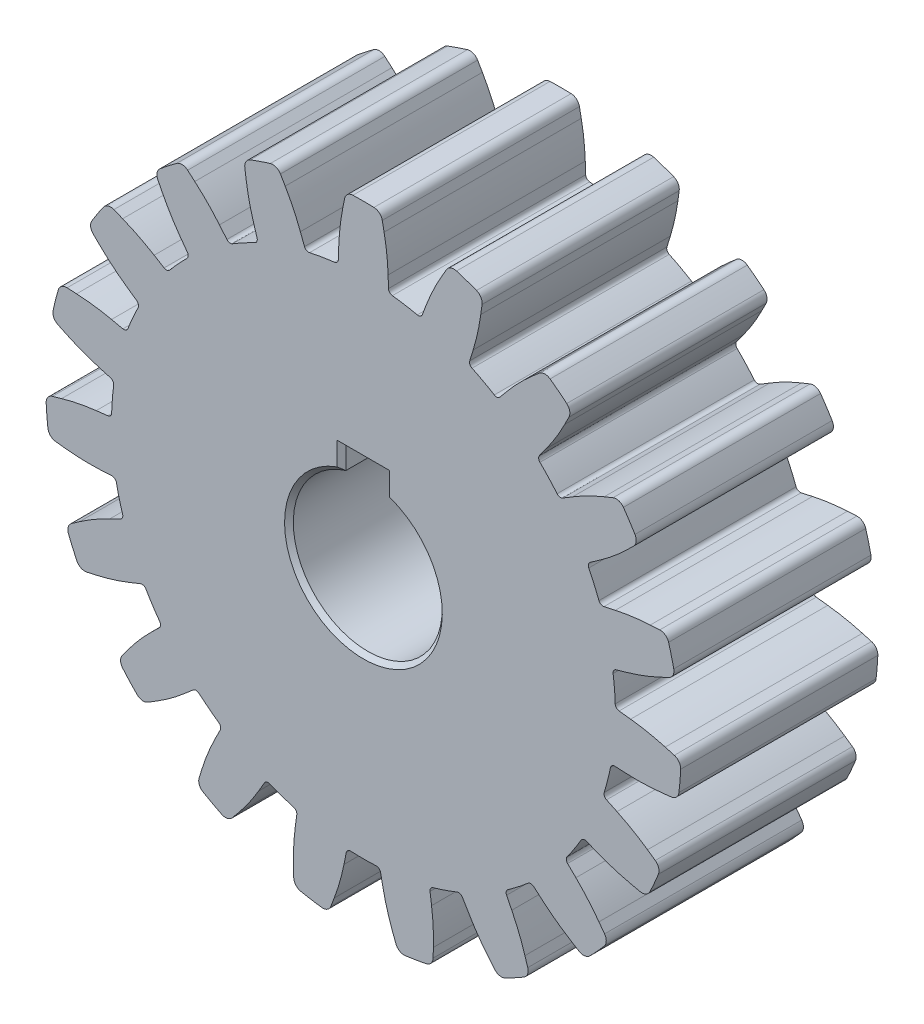
SolidWorks part; units mm, degrees
material "Plain Carbon Steel"
ref_plane "Front Plane" through (0, 0, 0) normal (0, 0, 1) x (1, 0, 0)
ref_plane "Top Plane" through (0, 0, 0) normal (0, 1, 0) x (1, 0, 0)
ref_plane "Right Plane" through (0, 0, 0) normal (1, 0, 0) x (0, 0, -1)
sketch "Sketch2" plane through (0, 0, 0) normal (0, 0, 1) x (1, 0, 0)
  line L0 (0, 0) -> (0, 72.5) construction
  line L1 (-5, 21.2481) -> (5, 21.2481)
  line L2 (5, 21.2481) -> (5, 16.2481)
  line L3 (-5, 21.2481) -> (-5, 16.2481)
  line L4 (-5.75, 57.2118) -> (-5.6336, 60.7298)
  line L5 (-4.7201, 68.7301) -> (-4.3035, 70.8473)
  line L6 (5.75, 57.2118) -> (5.6336, 60.7298)
  line L7 (4.7201, 68.7301) -> (4.3035, 70.8473)
  circle A0 centre (0, 0) radius 57.5
  circle A1 centre (0, 0) radius 58.5 construction
  circle A2 centre (0, 0) radius 65 construction
  circle A3 centre (0, 0) radius 72.5 construction
  arc A4 (-5, 16.2481) -> (5, 16.2481) centre (0, 0) ccw
  arc A5 (-2.4075, 72.46) -> (2.4075, 72.46) centre (0, 0) cw
  arc A6 (5.6336, 60.7298) -> (4.7201, 68.7301) centre (-44.3391, 59.0762) ccw
  arc A7 (-5.6336, 60.7298) -> (-4.7201, 68.7301) centre (44.3391, 59.0762) cw
  arc A8 (4.3035, 70.8473) -> (2.4075, 72.46) centre (2.3411, 70.4611) ccw
  arc A9 (-4.3035, 70.8473) -> (-2.4075, 72.46) centre (-2.3411, 70.4611) cw
  point P10 (0, 21.2481)
  point P21 (5.5, 64.7669)
  point P24 (-5.5, 64.7669)
  point P27 (4, 72.3896)
  point P30 (-4, 72.3896)
  dimension "D1" = 34
  dimension "D2" = 117
  dimension "D3" = 130
  dimension "D4" = 145
  dimension "D5" = 115
  dimension "D6" = 10
  dimension "D11" = 50
  dimension "D12" = 2
  dimension "D7" = 5
  dimension "D8" = 11.5
  dimension "D9" = 11
  dimension "D10" = 8
extrude "Boss-Extrude1" add sketch "Sketch2" along normal mid plane 45 contours A0 A4 L3 L1 L2 region at (0, 55.8737, 0)
extrude "Boss-Extrude2" add sketch "Sketch2<4>" along normal mid plane 45 contours A9 L5 A7 L4 A0 L6 A6 L7 A8 A5 region at (0, 64.4546, 0)
sketch "Sketch2<4>" plane through (0, 0, 0) normal (0, 0, 1) x (1, 0, 0) same geometry as "Sketch2"
pattern_circular "CirPattern1" count 19 over 360 about axis through (0, 0, 22.5) along (0, 0, -1) of "Boss-Extrude2"
chamfer "Chamfer1" distance 1 angle 45 8 edges at (5, 18.7481, -22.5) (0, 21.2481, -22.5) (-5, 18.7481, -22.5) (0, -17, -22.5) (5, 18.7481, 22.5) (0, 21.2481, 22.5) (-5, 18.7481, 22.5) (0, -17, 22.5)
fillet "Fillet1" radius 1 38 edges at (24.0151, 52.2449, 0) (13.1382, 55.9789, 0) (-5.75, 57.2118, 0) (5.75, 57.2118, 0) (30.6026, 48.6799, 0) (39.6778, 41.6164, 0) (44.7508, 36.1056, 0) (51.0407, 26.4782, 0) (54.0496, 19.6187, 0) (56.8727, 8.4706, 0) (57.4912, 1.0058, 0) (56.5415, -10.4549, 0) (54.7028, -17.716, 0) (50.0833, -28.2474, 0) (45.9864, -34.5181, 0) (38.1977, -42.9789, 0) (32.2868, -47.5796, 0) (22.1728, -53.053, 0) (15.0883, -55.4851, 0) (3.7452, -57.3779, 0) (-3.7452, -57.3779, 0) (-15.0883, -55.4851, 0) (-22.1728, -53.053, 0) (-32.2868, -47.5796, 0) (-38.1977, -42.9789, 0) (-45.9864, -34.5181, 0) (-50.0833, -28.2474, 0) (-54.7028, -17.716, 0) (-56.5415, -10.4549, 0) (-57.4912, 1.0058, 0) (-56.8727, 8.4706, 0) (-54.0496, 19.6187, 0) (-51.0407, 26.4782, 0) (-44.7508, 36.1056, 0) (-39.6778, 41.6164, 0) (-30.6026, 48.6799, 0) (-24.0151, 52.2449, 0) (-13.1382, 55.9789, 0)
